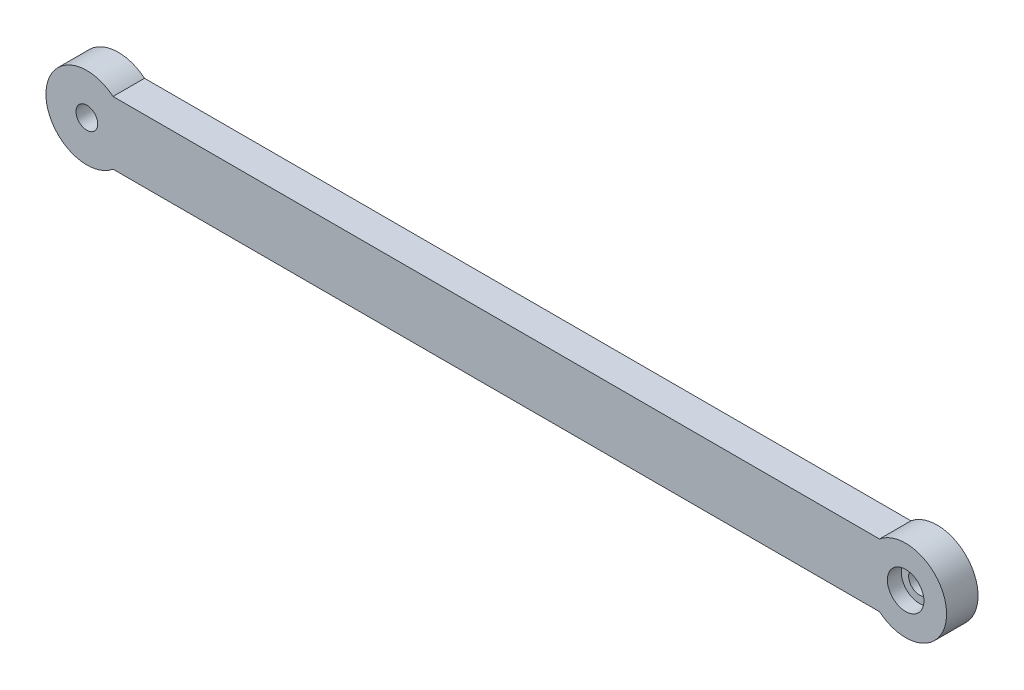
SolidWorks part; units mm, degrees
ref_plane "Front Plane" through (0, 0, 0) normal (0, 0, 1) x (1, 0, 0)
ref_plane "Top Plane" through (0, 0, 0) normal (0, 1, 0) x (1, 0, 0)
ref_plane "Right Plane" through (0, 0, 0) normal (1, 0, 0) x (0, 0, -1)
sketch "Sketch1" plane through (0, 0, 0) normal (0, 0, 1) x (1, 0, 0)
  line L0 (0, -5) -> (130, -5)
  line L1 (130, -5) -> (130, 5)
  line L2 (130, 5) -> (0, 5)
  line L3 (0, 5) -> (0, -5)
extrude "Boss-Extrude1" add sketch "Sketch1" along normal blind 5 from offset 3 offset against normal yes
sketch "Sketch2" plane through (0, 0, 0) normal (0, 0, 1) x (1, 0, 0)
  circle A0 centre (0, 0) radius 6.5
extrude "Boss-Extrude2" add sketch "Sketch2" along normal blind 5 from offset 3 offset against normal yes
sketch "Sketch3" plane through (0, 0, 0) normal (0, 0, 1) x (1, 0, 0)
  circle A0 centre (130, 0) radius 6.5
extrude "Boss-Extrude3" add sketch "Sketch3" along normal blind 5 from offset 3 offset against normal yes
sketch "Sketch4" plane through (0, 0, 0) normal (0, 0, 1) x (1, 0, 0)
  circle A0 centre (0, 0) radius 1.725
  circle A1 centre (130, 0) radius 1.725
extrude "Cut-Extrude1" cut sketch "Sketch4" against normal through all and the other way through all
sketch "Sketch5" plane through (0, 0, 0) normal (0, 0, 1) x (1, 0, 0)
  circle A0 centre (130, 0) radius 2.9
extrude "Cut-Extrude2" cut sketch "Sketch5" along normal blind 2.2 from offset 0.2 offset against normal yes
